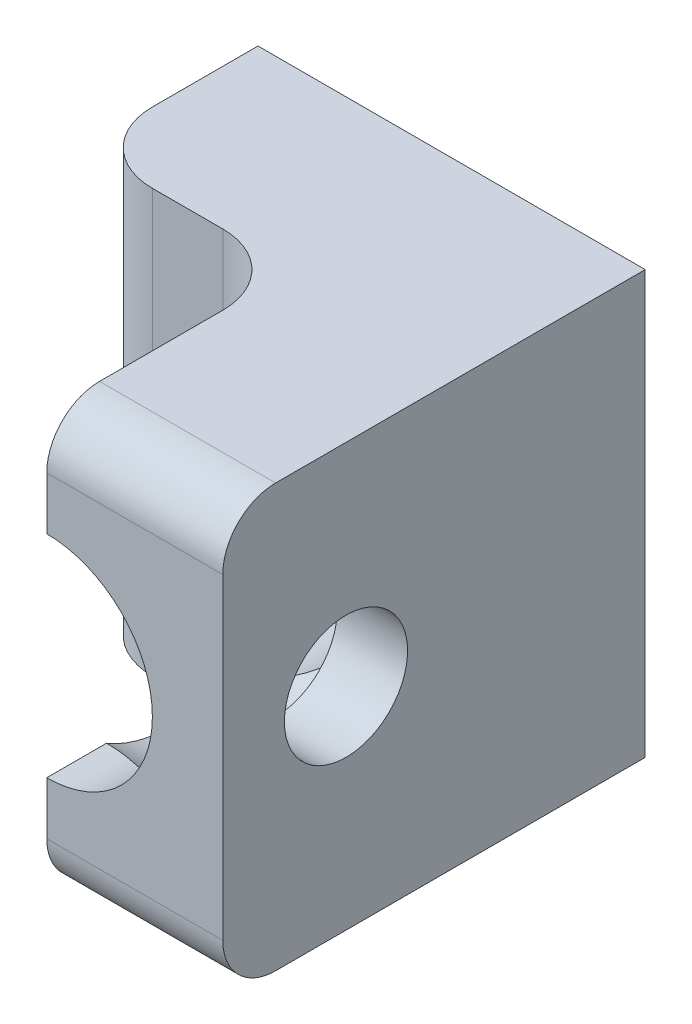
SolidWorks part; units mm, degrees
ref_plane "前视基准面" through (0, 0, 0) normal (0, 0, 1) x (1, 0, 0)
ref_plane "上视基准面" through (0, 0, 0) normal (0, 1, 0) x (1, 0, 0)
ref_plane "右视基准面" through (0, 0, 0) normal (1, 0, 0) x (0, 0, -1)
sketch "草图1" plane through (0, 0, 0) normal (0, 0, 1) x (1, 0, 0)
  line L1 (-6, -6) -> (6, -6)
  line L2 (-6, -6) -> (-6, 6)
  line L3 (-6, 6) -> (6, 6)
  line L4 (6, -6) -> (6, 6)
  line L5 (-6, -6) -> (6, 6) construction
  line L6 (-6, 6) -> (6, -6) construction
  circle A0 centre (0, 0) radius 3
extrude "凸台-拉伸1" add sketch "草图1" along normal blind 5
sketch "草图3" plane through (0, 0, 5) normal (0, 0, 1) x (1, 0, 0)
  line L0 (-6, -6) -> (6, -6) construction
  line L1 (6, -6) -> (6, 6) construction
  line L2 (6, 6) -> (-6, 6) construction
  line L3 (0, -6) -> (6, -6)
  line L4 (6, -6) -> (6, 6)
  line L5 (6, 6) -> (0, 6)
  line L6 (0, 3) -> (0, 6)
  line L7 (0, -3) -> (0, -6)
  circle A0 centre (0, 0) radius 3 construction
  arc A1 (0, -3) -> (0, 3) centre (0, 0) ccw
extrude "凸台-拉伸2" add sketch "草图3" along normal blind 7
sketch "草图4" plane through (0, 0, 0) normal (-1, 0, 0) x (0, 0, 1)
  circle A0 centre (8.5, 0) radius 1.75
extrude "切除-拉伸1" cut sketch "草图4" against normal blind 7
sketch "草图5" plane through (0, 0, 0) normal (-1, 0, 0) x (0, 0, 1)
  circle A0 centre (8.5, 0) radius 3.5
extrude "切除-拉伸2" cut sketch "草图5" against normal blind 3
fillet "圆角1" radius 2 2 edges at (0, -4.5, 5) (0, 4.5, 5)
fillet "圆角2" radius 1.5 2 edges at (3, -6, 12) (3, 6, 12)
fillet "圆角3" radius 2 1 edges at (-6, 0, 5)
sketch "草图6" plane through (6, 0, 0) normal (1, 0, 0) x (0, 0, -1)
  line L1 (-34.084, -10.9966) -> (17.084, -10.9966)
  line L2 (-34.084, -10.9966) -> (-34.084, 10.9966)
  line L3 (-34.084, 10.9966) -> (17.084, 10.9966)
  line L4 (17.084, -10.9966) -> (17.084, 10.9966)
  line L5 (-34.084, -10.9966) -> (17.084, 10.9966) construction
  line L6 (-34.084, 10.9966) -> (17.084, -10.9966) construction
  point P0 (-8.5, 0)
extrude "切除-拉伸3" cut sketch "草图6" against normal blind 1
